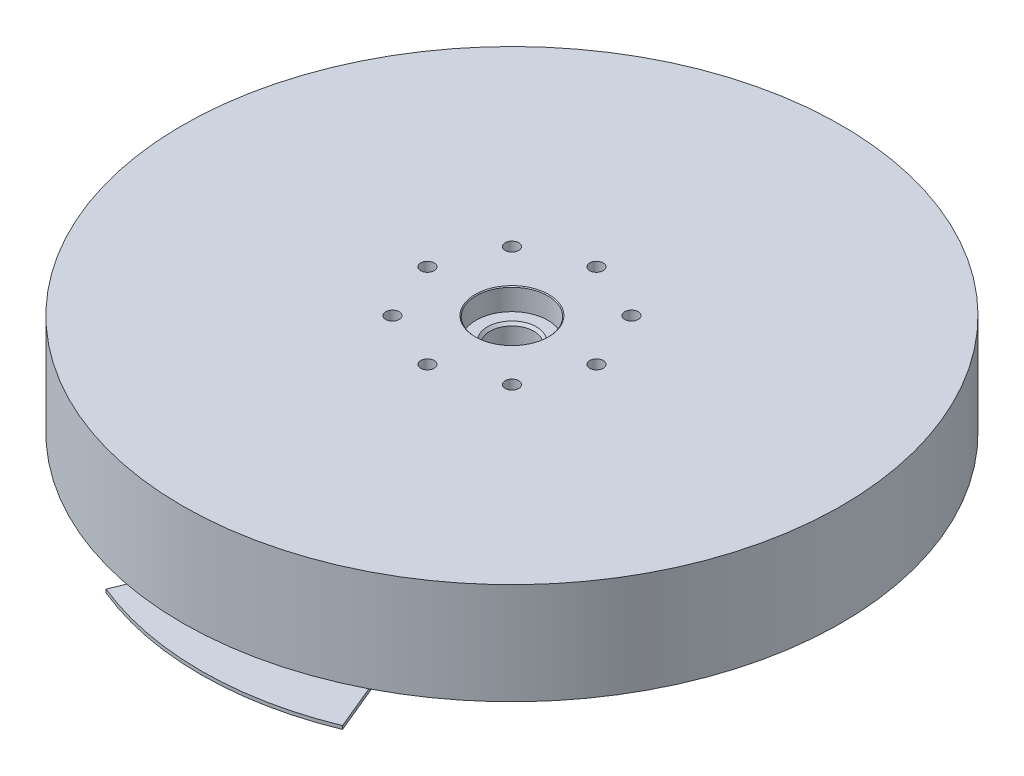
SolidWorks part; units mm, degrees
material "Ст 3 ГОСТ 380-88"
ref_plane "Front Plane" through (0, 0, 0) normal (0, 0, 1) x (1, 0, 0)
ref_plane "Top Plane" through (0, 0, 0) normal (0, 1, 0) x (1, 0, 0)
ref_plane "Right Plane" through (0, 0, 0) normal (1, 0, 0) x (0, 0, -1)
sketch "Sketch1" plane through (0, 0, 0) normal (1, 0, 0) x (0, 0, -1)
  line L0 (0, -14) -> (0, -31.7786) construction
  line L1 (-195, 60) -> (-195, 0)
  line L2 (-195, 0) -> (-185.5, 0)
  line L3 (-74.5, 0) -> (-74.5, -14)
  line L4 (-74.5, -14) -> (-20, -14)
  line L5 (-195, 60) -> (-185.5, 60)
  line L6 (0, 30.6711) -> (0, 60) construction
  line L7 (-17.5, 47) -> (-17.5, -11.5)
  line L8 (-17.5, -14) -> (0, -14) construction
  line L9 (0, 30.6711) -> (0, -14) construction
  line L10 (0, -14) -> (0, 30.6711) construction
  line L11 (-17.5, 60) -> (0, 60) construction
  line L12 (-20, 60) -> (-17.5, 57.5) construction
  line L13 (-20, -14) -> (-17.5, -11.5)
  line L14 (-21.25, 59.5) -> (-21.25, 47)
  line L15 (-21.25, 47) -> (-17.5, 47)
  line L16 (-21.25, 60) -> (-20, 60) construction
  line L17 (-17.5, 57.5) -> (-17.5, 47) construction
  line L18 (-21.75, 60) -> (-21.25, 59.5)
  line L19 (-185.5, 0) -> (-185.5, 10)
  line L20 (-185.5, 10) -> (-74.5, 10)
  line L21 (-74.5, 0) -> (-74.5, 10)
  line L22 (-185.5, 0) -> (-74.5, 0) construction
  line L23 (-185.5, 60) -> (-185.5, 50) construction
  line L24 (-185.5, 50) -> (-74.5, 50) construction
  line L25 (-74.5, 50) -> (-74.5, 60) construction
  line L26 (-185.5, 60) -> (-74.5, 60) construction
  line L27 (-74.5, 60) -> (-21.75, 60)
  line L28 (-185.5, 60) -> (-74.5, 60)
  dimension "D1" = 60
  dimension "D2" = 390
  dimension "D3" = 149
  dimension "D4" = 14
  dimension "D5" = 17.5
  dimension "D6" = 13
  dimension "D7" = 42.5
  dimension "D10" = 10
  dimension "D11" = 9.5
  dimension "D13" = 10
revolve "Revolve1" add sketch "Sketch1" angle 360 about L0
sketch "Sketch2" plane through (0, 60, 0) normal (0, 1, 0) x (1, 0, 0)
  line L0 (-50, 0) -> (0, 0) construction
  circle A0 centre (-50, 0) radius 4
  circle A1 centre (-35.3553, 35.3553) radius 4
  circle A2 centre (0, 50) radius 4
  circle A3 centre (35.3553, 35.3553) radius 4
  circle A4 centre (50, 0) radius 4
  circle A5 centre (35.3553, -35.3553) radius 4
  circle A6 centre (0, -50) radius 4
  circle A7 centre (-35.3553, -35.3553) radius 4
  point P21 (0, 0)
  dimension "D1" = 8
  dimension "D2" = 8
  dimension "D3" = 50
extrude "Cut-Extrude1" cut sketch "Sketch2" against normal through all both and the other way through all
sketch "Sketch3" plane through (0, 10, 0) normal (0, -1, 0) x (1, 0, 0)
  line L0 (0, 129.2853) -> (0, -136.9499) construction
  line L1 (0, 0) -> (0, 132.1781) construction
  line L2 (0, 0) -> (-104.479, 104.479) construction
  circle A0 centre (0, 82) radius 2
  circle A1 centre (0, 120) radius 2
  circle A2 centre (84.8528, 84.8528) radius 2
  circle A3 centre (57.9828, 57.9828) radius 2 construction
  circle A4 centre (120, 0) radius 2
  circle A5 centre (82, 0) radius 2
  circle A6 centre (84.8528, -84.8528) radius 2
  circle A7 centre (57.9828, -57.9828) radius 2 construction
  circle A8 centre (0, -120) radius 2
  circle A9 centre (0, -82) radius 2
  circle A10 centre (-84.8528, -84.8528) radius 2
  circle A11 centre (-57.9828, -57.9828) radius 2 construction
  circle A12 centre (-120, 0) radius 2
  circle A13 centre (-82, 0) radius 2
  circle A14 centre (-84.8528, 84.8528) radius 2
  circle A15 centre (-57.9828, 57.9828) radius 2 construction
  circle A16 centre (0, 0) radius 120 construction
  point P104 (0, 0)
  dimension "D1" = 4
  dimension "D4" = 120
  dimension "D3" = 240
  dimension "D2" = 82
  dimension "D6" = 45
  dimension "D5" = 8
extrude "Cut-Extrude2" [suppressed] cut sketch "Sketch3" against normal blind 15
ref_plane "Plane1" through (0, 30, 0) normal (0, -1, 0) x (-1, 0, 0)
mirror "Mirror1" [suppressed] about plane through (0, 30, 0) normal (0, -1, 0)
sketch "Sketch4" plane through (0, 60, 0) normal (0, 1, 0) x (1, 0, 0)
  circle A0 centre (0, 50) radius 8
  circle A1 centre (0, 0) radius 50 construction
  circle A2 centre (35.3553, 35.3553) radius 8
  circle A3 centre (50, 0) radius 8
  circle A4 centre (35.3553, -35.3553) radius 8
  circle A5 centre (0, -50) radius 8
  circle A6 centre (-35.3553, -35.3553) radius 8
  circle A7 centre (-50, 0) radius 8
  circle A8 centre (-35.3553, 35.3553) radius 8
  point P22 (0, 0)
  dimension "D1" = 16
  dimension "D2" = 8
extrude "Cut-Extrude3" [suppressed] cut sketch "Sketch4" against normal blind 12
sketch "Sketch5" plane through (0, -14, 0) normal (0, -1, 0) x (1, 0, 0)
  circle A0 centre (35.3553, -35.3553) radius 4 construction
  circle A1 centre (0, 0) radius 74.5
  circle A2 centre (0, 0) radius 74.5
  circle A3 centre (0, -50) radius 4 construction
  circle A4 centre (-35.3553, -35.3553) radius 4 construction
  circle A5 centre (-50, 0) radius 4 construction
  circle A6 centre (50, 0) radius 4 construction
  circle A7 centre (35.3553, 35.3553) radius 4 construction
  circle A8 centre (-35.3553, 35.3553) radius 4 construction
  circle A9 centre (0, 50) radius 4 construction
  circle A10 centre (35.3553, -35.3553) radius 4
  circle A11 centre (0, -50) radius 4
  circle A12 centre (-35.3553, -35.3553) radius 4
  circle A13 centre (-50, 0) radius 4
  circle A14 centre (50, 0) radius 4
  circle A15 centre (35.3553, 35.3553) radius 4
  circle A16 centre (-35.3553, 35.3553) radius 4
  circle A17 centre (0, 50) radius 4
  circle A18 centre (0, 0) radius 17.5 construction
  circle A19 centre (0, 0) radius 17.5
  dimension "D1" = 0
extrude "Boss-Extrude1" add sketch "Sketch5" along normal blind 1 from offset 30 separate body
sketch "Sketch6" plane through (0, -14, 0) normal (0, -1, 0) x (1, 0, 0)
  circle A1 centre (0, 0) radius 74.5
  circle A2 centre (0, 0) radius 74.5
  dimension "D1" = 0
extrude "Cut-Extrude4" cut sketch "Sketch6" against normal blind 2.5
chamfer "Chamfer1" [suppressed] distance 5 angle 60
chamfer "Chamfer2" [suppressed] distance 10 angle 30
sketch "Sketch7" plane through (0, 10, 0) normal (0, -1, 0) x (1, 0, 0)
  line L0 (0, 234.4435) -> (0, -294.1465) construction
  line L1 (0, 0) -> (28.7013, 69.291) construction
  line L3 (-28.7013, 69.291) -> (-70.4138, 169.9938) construction
  line L4 (28.2387, 69.4808) -> (69.9516, 170.1845)
  line L5 (-28.2387, 69.4808) -> (-69.9516, 170.1845)
  line L6 (28.7013, 69.291) -> (70.4138, 169.9938) construction
  line L7 (70.9878, 171.3797) -> (89.9519, 217.1632) construction
  line L8 (70.4138, 169.9938) -> (70.9878, 171.3797) construction
  line L9 (0, 75) -> (22.6048, 75) construction
  line L10 (0, 129.5) -> (22.6048, 129.5) construction
  line L11 (0, 184) -> (132.4756, 184) construction
  line L12 (47.6227, 177.7304) -> (0, 0) construction
  line L13 (-47.6227, 177.7304) -> (0, 0) construction
  line L14 (0, 0) -> (118.558, 205.3486) construction
  circle A1 centre (0, 0) radius 17.5 construction
  arc A2 (69.9516, 170.1845) -> (-69.9516, 170.1845) centre (0, 0) ccw
  circle A3 centre (0, 157) radius 2.6
  circle A4 centre (0, 0) radius 185.5 construction
  circle A6 centre (0, 102) radius 2.6
  arc A8 (-69.9516, 170.1845) -> (-70.4138, 169.9938) centre (0, 0) ccw construction
  arc A9 (28.2387, 69.4808) -> (-28.2387, 69.4808) centre (0, 0) ccw
  dimension "D1" = 22.5
  dimension "D2" = 184
  dimension "D3" = 371
  dimension "D5" = 0.5
  dimension "D6" = 75
  dimension "D7" = 5.2
  dimension "D4" = 109
  dimension "D8" = 54.5
  dimension "D9" = 55
  dimension "D10" = 15
  dimension "D11" = 15
extrude "Boss-Extrude3" add sketch "Sketch7" along normal blind 5 from offset 0.01 separate body
sketch "Sketch8" plane through (0, 4.99, 0) normal (0, -1, 0) x (1, 0, 0)
  line L2 (28.2387, 69.4808) -> (69.9516, 170.1845)
  line L3 (-69.9516, 170.1845) -> (-28.2387, 69.4808)
  line L4 (28.2387, 69.4808) -> (69.9516, 170.1845)
  line L5 (-69.9516, 170.1845) -> (-28.2387, 69.4808)
  circle A0 centre (0, 102) radius 2.6 construction
  circle A1 centre (0, 157) radius 2.6 construction
  arc A2 (28.2387, 69.4808) -> (-28.2387, 69.4808) centre (0, 0) ccw
  arc A3 (69.9516, 170.1845) -> (-69.9516, 170.1845) centre (0, 0) ccw
  arc A4 (28.2387, 69.4808) -> (-28.2387, 69.4808) centre (0, 0) ccw
  arc A5 (69.9516, 170.1845) -> (-69.9516, 170.1845) centre (0, 0) ccw
  circle A6 centre (0, 102) radius 2.6
  circle A7 centre (0, 157) radius 2.6
  dimension "D1" = 0
extrude "Boss-Extrude4" add sketch "Sketch8" along normal blind 5 separate body
chamfer "Chamfer3" distance 3.5 angle 45 2 edges at (0, -0.01, 99.4) (0, -0.01, 154.4)
chamfer "Chamfer4" distance 3.5 angle 45 2 edges at (0, 9.99, 104.6) (0, 9.99, 154.4)
sketch "Sketch9" plane through (0, 10, 0) normal (0, -1, 0) x (1, 0, 0)
  line L0 (0, 0) -> (0, 213.1478) construction
  circle A0 centre (0, 157) radius 2.6
  circle A1 centre (0, 157) radius 2.6 construction
  circle A3 centre (0, 102) radius 2.6
  circle A4 centre (0, 102) radius 2.6 construction
  circle A5 centre (111.0158, 111.0158) radius 2.6
  circle A6 centre (72.1249, 72.1249) radius 2.6
  circle A7 centre (157, 0) radius 2.6
  circle A8 centre (102, 0) radius 2.6
  circle A9 centre (111.0158, -111.0158) radius 2.6
  circle A10 centre (72.1249, -72.1249) radius 2.6
  circle A11 centre (0, -157) radius 2.6
  circle A12 centre (0, -102) radius 2.6
  circle A13 centre (-111.0158, -111.0158) radius 2.6
  circle A14 centre (-72.1249, -72.1249) radius 2.6
  circle A15 centre (-157, 0) radius 2.6
  circle A16 centre (-102, 0) radius 2.6
  circle A17 centre (-111.0158, 111.0158) radius 2.6
  circle A18 centre (-72.1249, 72.1249) radius 2.6
  point P42 (0, 0)
  dimension "D1" = 5.2
  dimension "D2" = 8
extrude "Cut-Extrude5" cut sketch "Sketch9" against normal blind 15
sketch "Sketch10" plane through (0, -0.01, 0) normal (0, -1, 0) x (1, 0, 0)
  line L0 (-30.5248, 75) -> (30.5248, 75)
  line L1 (28.2387, 69.4808) -> (69.9516, 170.1845) construction
  line L2 (30.5248, 75) -> (28.2387, 69.4808)
  line L3 (28.2387, 69.4808) -> (-28.2387, 69.4808)
  line L4 (-28.2387, 69.4808) -> (-30.5248, 75)
  point P3 (0, 75)
extrude "Cut-Extrude6" cut sketch "Sketch10" against normal blind 10
pattern_circular "CirPattern5" count 4 over 360 about axis through (0, -14, 0) along (0, 1, 0) reverse direction yes of bodies 119 120
sketch "Sketch11" plane through (0, -0.01, 0) normal (0, -1, 0) x (1, 0, 0)
  line L3 (-30.5248, 75) -> (30.5248, 75)
  line L4 (30.5248, 75) -> (69.9516, 170.1845)
  line L5 (-69.9516, 170.1845) -> (-30.5248, 75)
  line L6 (-30.5248, 75) -> (30.5248, 75)
  line L7 (30.5248, 75) -> (69.9516, 170.1845)
  line L8 (-69.9516, 170.1845) -> (-30.5248, 75)
  arc A1 (69.9516, 170.1845) -> (-69.9516, 170.1845) centre (0, 0) ccw
  arc A2 (69.9516, 170.1845) -> (-69.9516, 170.1845) centre (0, 0) ccw
  dimension "D1" = 0
extrude "Boss-Extrude5" add sketch "Sketch11" along normal blind 2 from offset 30 separate body contours L6 L7 A2 L8
sketch "Sketch12" plane through (0, -11.5, 0) normal (0, -1, 0) x (1, 0, 0)
  circle A0 centre (0, 0) radius 13
  circle A1 centre (0, 0) radius 23
  dimension "D1" = 46
  dimension "D2" = 26
extrude "Boss-Extrude6" add sketch "Sketch12" against normal up to surface (58.5 mm away) and the other way blind 20 up to face at (0, 47, 21.25)
chamfer "Chamfer5" distance 1.5 angle 45 1 edges at (0, -31.5, -23)
thread "Thread1" pitch 1.5 method cut trim with start face yes trim with end face yes profile "Thread Profile1" start angle 0, offset 10, length 0, pitch 1.5, diameter 46
ref_plane "Plane2" through (23, -40, 0) normal (0, 0, 1) x (1, 0, 0)
sketch "Thread Profile1" plane through (23, -40, 0) normal (0, 0, 1) x (1, 0, 0)
  line L0 (0, 0) -> (0, 1.5) construction
  line L11 (0, 0) -> (0, 1.3125)
  line L12 (0, 1.3125) -> (-0.8119, 0.8437)
  line L13 (-0.8119, 0.8437) -> (-0.8119, 0.4687)
  line L15 (-0.8119, 0.4687) -> (0, 0)
  line L17 (-0.8119, 0.6562) -> (0, 0.6562) construction
  point P2 (0, 0)
  dimension "Pitch" = 1.5
  dimension "Profile_Angle" = 60
  dimension "Profile_Land" = 0.375
  dimension "Profile_Height" = 0.8119
chamfer "Chamfer6" distance 1.5 angle 45 2 edges at (0, 47, 13) (0, -31.5, -13)
